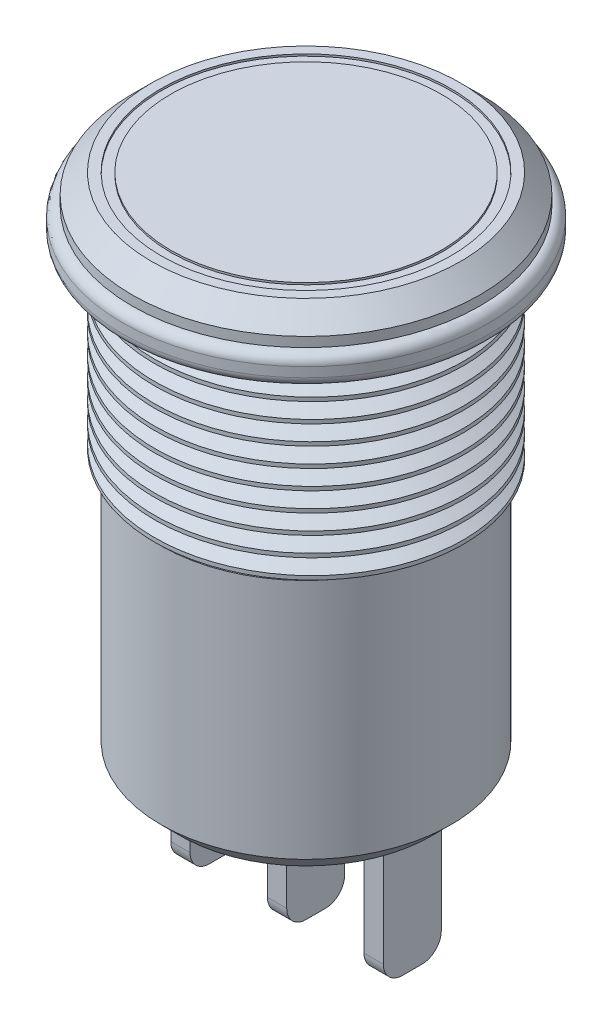
SolidWorks part; units mm, degrees
material "1023 碳钢板 (SS)"
ref_plane "前视基准面" through (0, 0, 0) normal (0, 0, 1) x (1, 0, 0)
ref_plane "上视基准面" through (0, 0, 0) normal (0, 1, 0) x (1, 0, 0)
ref_plane "右视基准面" through (0, 0, 0) normal (1, 0, 0) x (0, 0, -1)
sketch "草图1" plane through (0, 0, 0) normal (0, 1, 0) x (1, 0, 0)
  circle A0 centre (0, 0) radius 8
extrude "凸台-拉伸1" add sketch "草图1" along normal blind 10
sketch "草图2" plane through (0, 10, 0) normal (0, 1, 0) x (1, 0, 0)
  circle A0 centre (0, 0) radius 9.5
extrude "凸台-拉伸2" add sketch "草图2" along normal blind 1.5
sketch "草图3" plane through (0, 11.5, 0) normal (0, 1, 0) x (1, 0, 0)
  circle A0 centre (0, 0) radius 9
extrude "凸台-拉伸3" add sketch "草图3" along normal blind 1.5
sketch "草图7" plane through (0, 10, 0) normal (0, -1, 0) x (-1, 0, 0)
  circle A0 centre (0, 0) radius 8 construction
  circle A1 centre (0, 0) radius 8
curve "螺旋线/涡状线1" pitch 1 height 10 radius 8 left hand yes centre (0, 10, 0) axis (0, -1, 0) start towards (0, 0, -1)
sketch "草图8" plane through (0, 0, 0) normal (1, 0, 0) x (0, 0, -1)
  line L8 (8, 0) -> (8, 10) construction
  line L9 (8, 10) -> (8.5, 10)
  line L10 (7.3, 9.6) -> (8, 10)
  line L11 (7.3, 9.6) -> (8, 9.2)
  line L12 (-9.5, 10) -> (9.5, 10) construction
  line L13 (8.5, 10) -> (8.5, 9.2)
  line L14 (8.5, 9.2) -> (8, 9.2)
sweep "切除-扫描1" cut profiles "草图8" path "螺旋线/涡状线1" align with end faces yes
sketch "草图9" plane through (0, 0, 0) normal (0, -1, 0) x (-1, 0, 0)
  circle A0 centre (0, 0) radius 7.5
extrude "凸台-拉伸6" add sketch "草图9" along normal blind 13.5
sketch "草图12" plane through (0, 13, 0) normal (0, 1, 0) x (1, 0, 0)
  circle A0 centre (0, 0) radius 7.5
  circle A1 centre (0, 0) radius 7
extrude "切除-拉伸1" cut sketch "草图12" against normal blind 0.1
sketch "草图13" plane through (0, -13.5, 0) normal (0, -1, 0) x (-1, 0, 0)
  line L1 (-0.5, 1.5) -> (-0.5, -1.5)
  line L2 (-5.5, 1.5) -> (-4.5, 1.5)
  line L3 (-5.5, 1.5) -> (-5.5, -1.5)
  line L4 (-5.5, -1.5) -> (-4.5, -1.5)
  line L5 (-4.5, 1.5) -> (-4.5, -1.5)
  line L6 (-5.5, 1.5) -> (-4.5, -1.5) construction
  line L7 (-5.5, -1.5) -> (-4.5, 1.5) construction
  line L8 (-0.5, 1.5) -> (0.5, 1.5)
  line L9 (0.5, 1.5) -> (0.5, -1.5)
  line L10 (-0.5, -1.5) -> (0.5, -1.5)
  line L11 (4.5, 1.5) -> (4.5, -1.5)
  line L12 (4.5, 1.5) -> (5.5, 1.5)
  line L13 (5.5, 1.5) -> (5.5, -1.5)
  line L14 (4.5, -1.5) -> (5.5, -1.5)
  dimension "D1" = 3
extrude "凸台-拉伸9" add sketch "草图13" along normal blind 6.5
fillet "圆角2" radius 1 6 edges at (-5, -20, 1.5) (-5, -20, -1.5) (0, -20, -1.5) (0, -20, 1.5) (5, -20, 1.5) (5, -20, -1.5)
chamfer "倒角3" distance 1 angle 45 2 edges at (0, -13.5, -7.5) (0, 13, 9)
fillet "圆角3" radius 0.5 2 edges at (0, 10, 9.5) (0, 11.5, 9.5)
